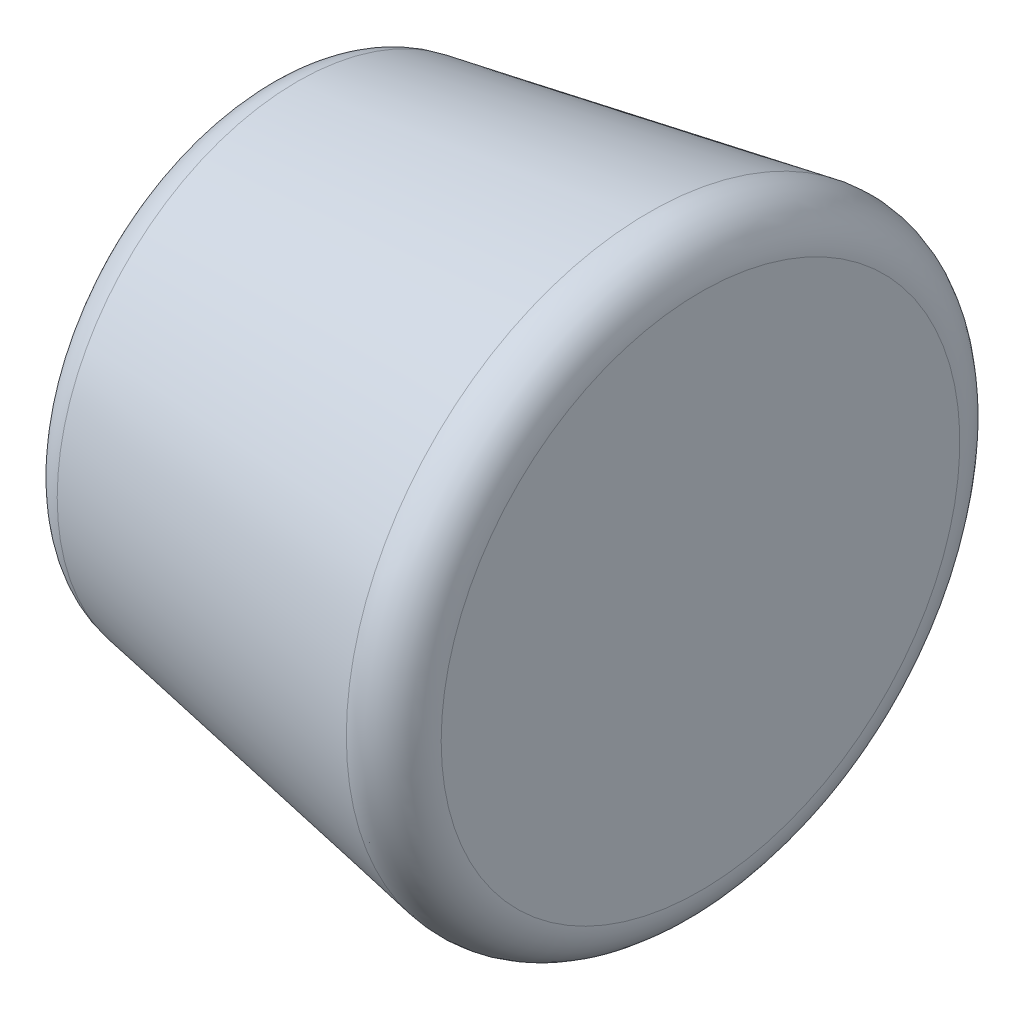
SolidWorks part; units mm, degrees
material "PLA"
ref_plane "Front Plane" through (0, 0, 0) normal (0, 0, 1) x (1, 0, 0)
ref_plane "Top Plane" through (0, 0, 0) normal (0, 1, 0) x (1, 0, 0)
ref_plane "Right Plane" through (0, 0, 0) normal (1, 0, 0) x (0, 0, -1)
sketch "Sketch1" plane through (0, 0, 0) normal (0, 0, 1) x (1, 0, 0)
  line L0 (0, 0) -> (0, 5.323)
  line L1 (55, 0) -> (-55, 0) construction
  line L2 (0, 5.323) -> (10, 7.096)
  line L3 (10, 7.096) -> (10, 0)
  line L4 (10, 0) -> (0, 0)
  line L5 (0, 5.323) -> (10, 5.323)
  line L6 (0, -55) -> (0, 55) construction
  dimension "D1" = 5.323
  dimension "D2" = 7.096
  dimension "D3" = 10
revolve "Revolve1" add sketch "Sketch1" angle 360 about L4 region at (5, 2.6615, 0) region at (6.6667, 5.914, 0)
fillet "Fillet1" radius 1 2 edges at (0, 0, -5.323) (10, 0, -7.096)
